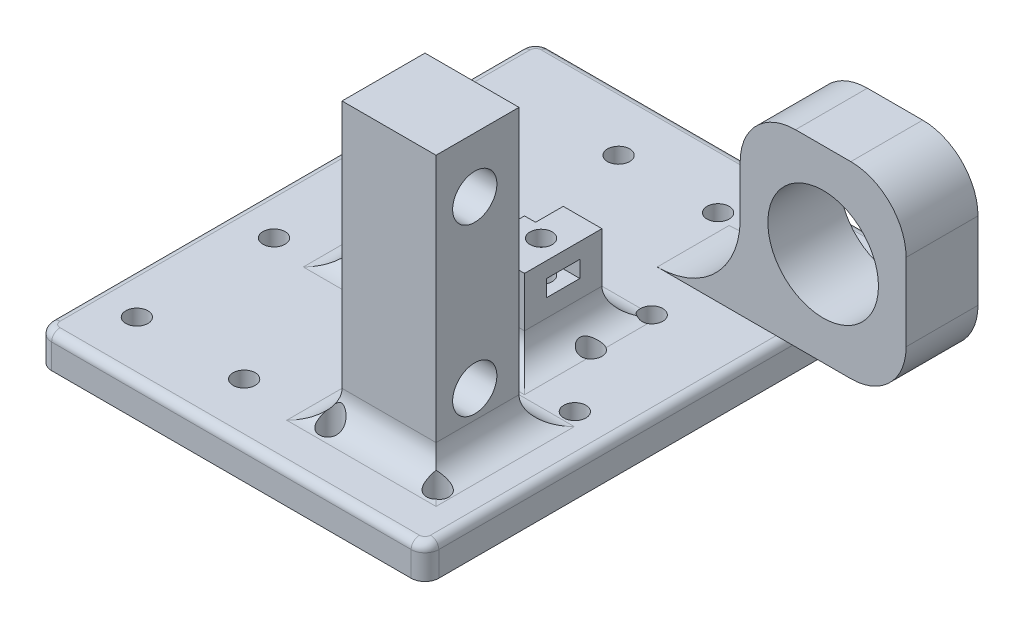
SolidWorks part; units mm, degrees
ref_plane "Front Plane" through (0, 0, 0) normal (0, 0, 1) x (1, 0, 0)
ref_plane "Top Plane" through (0, 0, 0) normal (0, 1, 0) x (1, 0, 0)
ref_plane "Right Plane" through (0, 0, 0) normal (1, 0, 0) x (0, 0, -1)
sketch "Sketch1" plane through (0, 0, 0) normal (0, 1, 0) x (1, 0, 0)
  line L0 (-8.0156, -1.4008) -> (61.9844, -1.4008)
  line L1 (-8.0156, 43.5992) -> (61.9844, 43.5992)
  line L2 (-8.0156, 43.5992) -> (-8.0156, -46.4008)
  line L3 (-8.0156, -46.4008) -> (61.9844, -46.4008)
  line L4 (61.9844, 43.5992) -> (61.9844, -46.4008)
  line L5 (26.9844, 43.5992) -> (26.9844, -46.4008)
  line L6 (9.4844, -1.4008) -> (9.4844, -46.4008)
  line L7 (-8.0156, -23.9008) -> (61.9844, -23.9008)
  circle A0 centre (17.9844, 32.5992) radius 3
  circle A1 centre (17.9844, 32.5992) radius 2
  circle A2 centre (18.095, 8.5992) radius 3
  circle A3 centre (18.095, 8.5992) radius 2
  circle A4 centre (35.8739, 8.5992) radius 2
  circle A5 centre (35.8739, 8.5992) radius 3
  circle A6 centre (35.9844, 32.5992) radius 2
  circle A7 centre (35.9844, 32.5992) radius 3
  circle A8 centre (19.1844, -11.5008) radius 2
  circle A9 centre (19.1844, -11.5008) radius 3
  circle A10 centre (-0.2156, -11.5008) radius 3
  circle A11 centre (-0.2156, -11.5008) radius 2
  circle A12 centre (-0.2156, -36.3008) radius 2
  circle A13 centre (19.1844, -36.3008) radius 3
  circle A14 centre (19.1844, -36.3008) radius 2
  circle A15 centre (-0.2156, -36.3008) radius 3
  circle A16 centre (54.1844, -36.3008) radius 2
  circle A17 centre (54.1844, -36.3008) radius 3
  circle A18 centre (34.7844, -36.3008) radius 2
  circle A19 centre (34.7844, -36.3008) radius 3
  circle A20 centre (34.7844, -11.5008) radius 3
  circle A21 centre (34.7844, -11.5008) radius 2
  circle A22 centre (54.1844, -11.5008) radius 2
  circle A23 centre (54.1844, -11.5008) radius 3
  dimension "D3" = 9
  dimension "D1" = 90
  dimension "D2" = 70
  dimension "D4" = 11
  dimension "D5" = 24
  dimension "D6" = 10.1
  dimension "D7" = 7.8
  dimension "D8" = 17.5
  dimension "D9" = 22.5
extrude "Boss-Extrude1" add sketch "Sketch1" along normal blind 6 contours L5 L1 L2 L0 A2 A0 | L1 L5 L0 L4 A5 A7 | A7 A6 | A0 A1 | A2 A3 | A5 A4 | L7 L6 L3 L5 A13 | L6 L7 L5 L0 A9 | L2 L7 L6 L0 A10 | L5 L7 L4 L0 A20 A23 | L7 L5 L3 L4 A17 A19 | L7 L2 L3 L6 A15 | A10 A11 | A9 A8 | A20 A21 | A23 A22 | A17 A16 | A13 A14 | A15 A12 | A19 | A18 region at (9.1658, 0, -21.1178) region at (0.7344, 0, 1.6858) region at (18.2344, 0, 1.6858) region at (0.7344, 0, 24.1858) region at (44.803, 0, -21.1178) region at (44.4844, 0, 12.7397) region at (18.2344, 0, 24.1858) region at (44.4844, 0, 35.0618) region at (15.0693, 0, -32.5992) region at (15.1799, 0, -8.5992) region at (32.9587, 0, -8.5992) region at (33.0693, 0, -32.5992) region at (16.2693, 0, 11.5008) region at (-3.1307, 0, 11.5008) region at (16.2693, 0, 36.3008) region at (-3.1307, 0, 36.3008) region at (51.2693, 0, 36.3008) region at (31.8693, 0, 11.5008) region at (51.2693, 0, 11.5008)
sketch "Sketch3" plane through (0, 6, 0) normal (0, 1, 0) x (1, 0, 0)
  line L0 (26.9844, 43.5992) -> (26.9844, -46.4008)
  line L1 (11.9844, 5.5992) -> (41.9844, 5.5992)
  line L2 (11.9844, 5.5992) -> (11.9844, -8.4008)
  line L3 (11.9844, -8.4008) -> (41.9844, -8.4008)
  line L4 (41.9844, 5.5992) -> (41.9844, -8.4008)
  line L5 (-8.0156, 43.5992) -> (61.9844, 43.5992) construction
  line L6 (-8.0156, -46.4008) -> (61.9844, -46.4008) construction
  line L7 (-8.0156, -1.4008) -> (61.9844, -1.4008)
  line L8 (-8.0156, 43.5992) -> (-8.0156, -46.4008) construction
  line L9 (61.9844, 43.5992) -> (61.9844, -46.4008) construction
  dimension "D1" = 14
  dimension "D2" = 30
  dimension "D3" = 7
  dimension "D4" = 15
extrude "Boss-Extrude2" add sketch "Sketch3" along normal blind 14 contours L2 L7 L0 L1 | L0 L7 L4 L1 | L7 L0 L3 L4 | L7 L2 L3 L0 region at (34.4844, 6, -2.0992) region at (19.4844, 6, -2.0992) region at (34.4844, 6, 4.9008) region at (19.4844, 6, 4.9008)
fillet "Fillet1" radius 2.5 4 edges at (-8.0156, 3, -43.5992) (61.9844, 3, -43.5992) (61.9844, 3, 46.4008) (-8.0156, 3, 46.4008)
fillet "Fillet2" radius 1.5 8 edges at (26.9844, 6, -43.5992) (-7.2833, 6, 45.6685) (61.2522, 6, 45.6685) (26.9844, 6, 46.4008) (61.2522, 6, -42.867) (61.9844, 6, 1.4008) (-7.2833, 6, -42.867) (-8.0156, 6, 1.4008)
sketch "Sketch4" plane through (0, 20, 0) normal (0, 1, 0) x (1, 0, 0)
  line L0 (26.9844, 42.0992) -> (26.9844, -44.9008)
  line L1 (59.4844, 42.0992) -> (-5.5156, 42.0992) construction
  line L2 (-5.5156, -44.9008) -> (59.4844, -44.9008) construction
  line L3 (-6.5156, -1.4008) -> (60.4844, -1.4008)
  line L4 (-6.5156, 41.0992) -> (-6.5156, -43.9008) construction
  line L5 (60.4844, -43.9008) -> (60.4844, 41.0992) construction
  circle A0 centre (15.9844, -1.4008) radius 2
  circle A1 centre (37.9844, -1.4008) radius 2
  dimension "D1" = 11
extrude "Cut-Extrude1" cut sketch "Sketch4" against normal blind 22 contours L3 A0 | L3 A0 | A1 L3 | A1 L3 region at (15.9844, 20, 0.552) region at (37.9844, 20, 0.552) region at (37.9844, 20, 2.2496) region at (15.9844, 20, 2.2496)
sketch "Sketch5" plane through (0, 0, -5.5992) normal (0, 0, -1) x (-1, 0, 0)
  line L0 (-11.9844, 20) -> (-41.9844, 20) construction
  line L1 (-34.9844, 20) -> (-18.9844, 20)
  circle A0 centre (-26.9844, 20) radius 8
  circle A1 centre (-26.9844, 20) radius 6
extrude "Cut-Extrude2" cut sketch "Sketch5" against normal blind 22 contours A1
sketch "Sketch6" plane through (0, 0, -5.5992) normal (0, 0, -1) x (-1, 0, 0)
  line L0 (-18.9844, 20) -> (-34.9844, 20)
  circle A0 centre (-26.9844, 20) radius 8
  circle A1 centre (-26.9844, 20) radius 6
  circle A2 centre (-26.9844, 20) radius 6
  circle A3 centre (-26.9844, 20) radius 8
  arc M1 (-20.9844, 20) -> (-32.9844, 20) centre (-26.9844, 20) cw
  line M2 (-32.9844, 20) -> (-41.9844, 20)
  line M6 (-11.9844, 20) -> (-20.9844, 20)
  dimension "D1" = 12
  dimension "D2" = 16
extrude "Cut-Extrude4" cut sketch "Sketch6" against normal blind 5 contours A0 M2 M6 M1 region at (26.9844, 12.1789, -5.5992)
sketch "Sketch9" plane through (0, 0, 8.4008) normal (0, 0, 1) x (1, 0, 0)
  circle A0 centre (26.9844, 20) radius 6
  circle A1 centre (26.9844, 20) radius 8
extrude "Cut-Extrude5" cut sketch "Sketch9" against normal blind 5
fillet "Fillet3" radius 5 4 edges at (26.9844, 6, 8.4008) (11.9844, 6, 1.4008) (26.9844, 6, -5.5992) (41.9844, 6, 1.4008)
sketch "Sketch10" plane through (0, 6, 0) normal (0, 1, 0) x (1, 0, 0)
  line L0 (53.9844, 42.0992) -> (53.9844, -44.9008)
  line L1 (59.4844, 42.0992) -> (-5.5156, 42.0992) construction
  line L2 (-5.5156, -44.9008) -> (59.4844, -44.9008) construction
  line L3 (26.9844, 43.5992) -> (26.9844, -46.4008)
  line L4 (-5.5156, 43.5992) -> (59.4844, 43.5992) construction
  line L5 (59.4844, -46.4008) -> (-5.5156, -46.4008) construction
  line L6 (26.9844, -1.4008) -> (60.4844, -1.4008)
  line L7 (53.9844, 31.5992) -> (83.9844, 31.5992)
  line L8 (53.9844, 31.5992) -> (53.9844, 18.5992)
  line L9 (53.9844, 18.5992) -> (83.9844, 18.5992)
  line L10 (83.9844, 31.5992) -> (83.9844, 18.5992)
  line L11 (60.4844, -43.9008) -> (60.4844, 41.0992) construction
  dimension "D1" = 27
  dimension "D2" = 30
  dimension "D3" = 20
  dimension "D4" = 13
extrude "Boss-Extrude5" add sketch "Sketch10" along normal blind 34 contours L7 L10 L9 L8
sketch "Sketch13" plane through (0, 0, -18.5992) normal (0, 0, 1) x (1, 0, 0)
  line L0 (68.9844, 40) -> (68.9844, 6)
  line L1 (53.9844, 40) -> (83.9844, 40) construction
  line L2 (60.4844, 6) -> (83.9844, 6) construction
  line L3 (53.9844, 23) -> (83.9844, 23)
  line L4 (53.9844, 40) -> (53.9844, 6) construction
  line L5 (83.9844, 40) -> (83.9844, 6) construction
  circle A0 centre (68.9844, 23) radius 10
extrude "Cut-Extrude6" cut sketch "Sketch13" against normal blind 34 contours L0 A0 L3 | L3 A0 L0 | L0 A0 L3 | L3 A0 L0 region at (73.2286, 27.2441, -18.5992) region at (64.7403, 27.2441, -18.5992) region at (73.2286, 18.7559, -18.5992) region at (64.7403, 18.7559, -18.5992)
fillet "Fillet5" radius 10 3 edges at (83.9844, 6, -25.0992) (53.9844, 40, -25.0992) (83.9844, 40, -25.0992)
sketch "Sketch14" plane through (0, 6, 0) normal (0, 1, 0) x (1, 0, 0)
  line L0 (-5.5156, -44.9008) -> (59.4844, -44.9008) construction
  line L1 (51.4844, -33.9008) -> (34.4844, -33.9008)
  line L2 (51.4844, -33.9008) -> (51.4844, -18.9008)
  line L3 (51.4844, -18.9008) -> (34.4844, -18.9008)
  line L4 (34.4844, -33.9008) -> (34.4844, -18.9008)
  line L5 (60.4844, -43.9008) -> (60.4844, 18.5992) construction
  dimension "D1" = 15
  dimension "D2" = 11
  dimension "D3" = 17
  dimension "D4" = 9
extrude "Boss-Extrude6" add sketch "Sketch14" along normal blind 50
sketch "Sketch15" plane through (51.4844, 0, 0) normal (1, 0, 0) x (0, 0, -1)
  line L0 (-33.9008, 6) -> (-18.9008, 6) construction
  line L1 (-33.9008, 56) -> (-33.9008, 6) construction
  circle A0 centre (-26.9008, 16) radius 4
  circle A1 centre (-26.9008, 46) radius 4
  dimension "D1" = 30
  dimension "D2" = 10
  dimension "D3" = 7
  dimension "D4" = 7
extrude "Cut-Extrude7" cut sketch "Sketch15" against normal blind 12
sketch "Sketch17" plane through (51.4844, 0, 0) normal (1, 0, 0) x (0, 0, -1)
  circle A0 centre (-26.9008, 46) radius 2.5
  circle A1 centre (-26.9008, 16) radius 2.5
extrude "Cut-Extrude8" cut sketch "Sketch17" against normal blind 30
fillet "Fillet9" radius 5 4 edges at (51.4844, 6, 26.4008) (42.9844, 6, 18.9008) (34.4844, 6, 26.4008) (42.9844, 6, 33.9008)
sketch "Sketch19" plane through (41.9844, 0, 0) normal (1, 0, 0) x (0, 0, -1)
  line L0 (5.5992, 20) -> (-8.4008, 20) construction
  line L1 (-4.4008, 17.2) -> (1.5992, 17.2)
  line L2 (-4.4008, 17.2) -> (-4.4008, 14.2)
  line L3 (-4.4008, 14.2) -> (1.5992, 14.2)
  line L4 (1.5992, 17.2) -> (1.5992, 14.2)
  line L5 (-8.4008, 20) -> (-8.4008, 11) construction
  point P6 (-8.4008, 15.5)
  dimension "D1" = 3
  dimension "D2" = 6
  dimension "D3" = 2.8
  dimension "D4" = 4
extrude "Cut-Extrude9" cut sketch "Sketch19" against normal blind 6.5
sketch "Sketch20" plane through (11.9844, 0, 0) normal (-1, 0, 0) x (0, 0, 1)
  line L0 (-5.5992, 20) -> (8.4008, 20) construction
  line L1 (-1.5992, 17.2) -> (4.4008, 17.2)
  line L2 (-1.5992, 17.2) -> (-1.5992, 14.2)
  line L3 (-1.5992, 14.2) -> (4.4008, 14.2)
  line L4 (4.4008, 17.2) -> (4.4008, 14.2)
  line L5 (8.4008, 20) -> (8.4008, 11) construction
  dimension "D1" = 6
  dimension "D2" = 3
  dimension "D3" = 2.8
  dimension "D4" = 4
extrude "Cut-Extrude10" cut sketch "Sketch20" against normal blind 6.5
fillet "Fillet10" radius 15 1 edges at (53.9844, 6, -25.0992)
sketch "Sketch22" plane through (0, 6, 0) normal (0, 1, 0) x (1, 0, 0)
  line L0 (-8.0156, -43.9008) -> (-8.0156, 41.0992) construction
  line L1 (-5.5156, 43.5992) -> (59.4844, 43.5992) construction
  circle A0 centre (7.9844, 10.5992) radius 2
  circle A1 centre (7.9844, 10.5992) radius 3
  circle A2 centre (45.9844, 10.5992) radius 3
  circle A3 centre (45.9844, 10.5992) radius 2
  circle A4 centre (45.9844, -0.4008) radius 3
  circle A5 centre (45.9844, -0.4008) radius 2
  circle A6 centre (7.9844, -0.4008) radius 2
  circle A7 centre (7.9844, -0.4008) radius 3
  dimension "D1" = 16
  dimension "D2" = 33
extrude "Cut-Extrude14" cut sketch "Sketch22" against normal through all both and the other way through all contours A6 | A0 | A3 | A5
